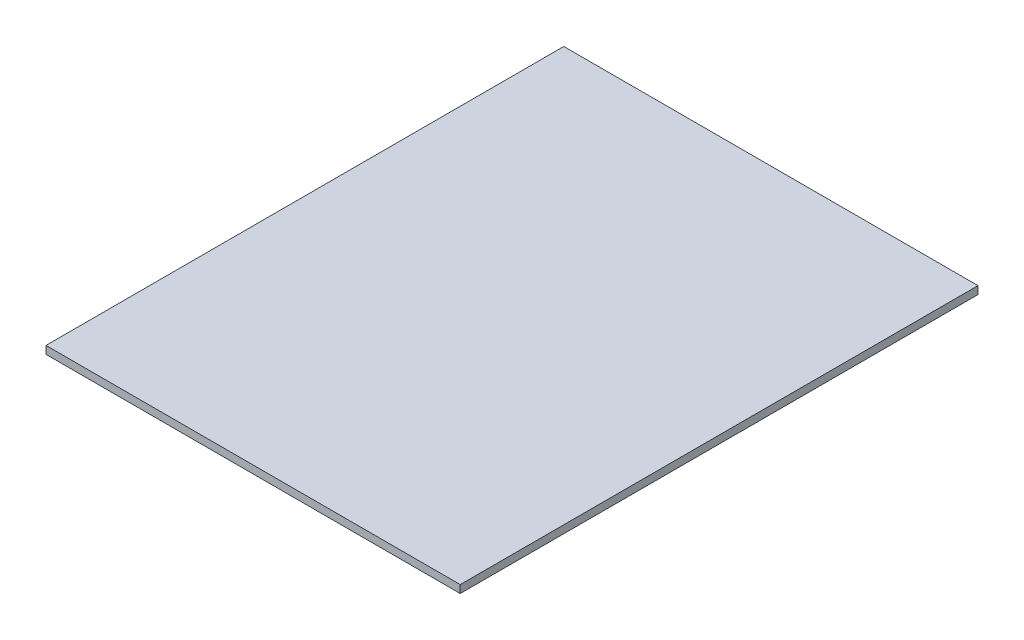
SolidWorks part; units mm, degrees
ref_plane "Front Plane" through (0, 0, 0) normal (0, 0, 1) x (1, 0, 0)
ref_plane "Top Plane" through (0, 0, 0) normal (0, 1, 0) x (1, 0, 0)
ref_plane "Right Plane" through (0, 0, 0) normal (1, 0, 0) x (0, 0, -1)
sketch "Sketch1" plane through (0, 0, 0) normal (0, 1, 0) x (1, 0, 0)
  line L1 (-80, -100) -> (80, -100)
  line L2 (-80, -100) -> (-80, 100)
  line L3 (-80, 100) -> (80, 100)
  line L4 (80, -100) -> (80, 100)
  line L5 (-80, -100) -> (80, 100) construction
  line L6 (-80, 100) -> (80, -100) construction
  point P0 (0, 0)
  dimension "D1" = 160
  dimension "D2" = 200
extrude "Boss-Extrude1" add sketch "Sketch1" along normal blind 3
